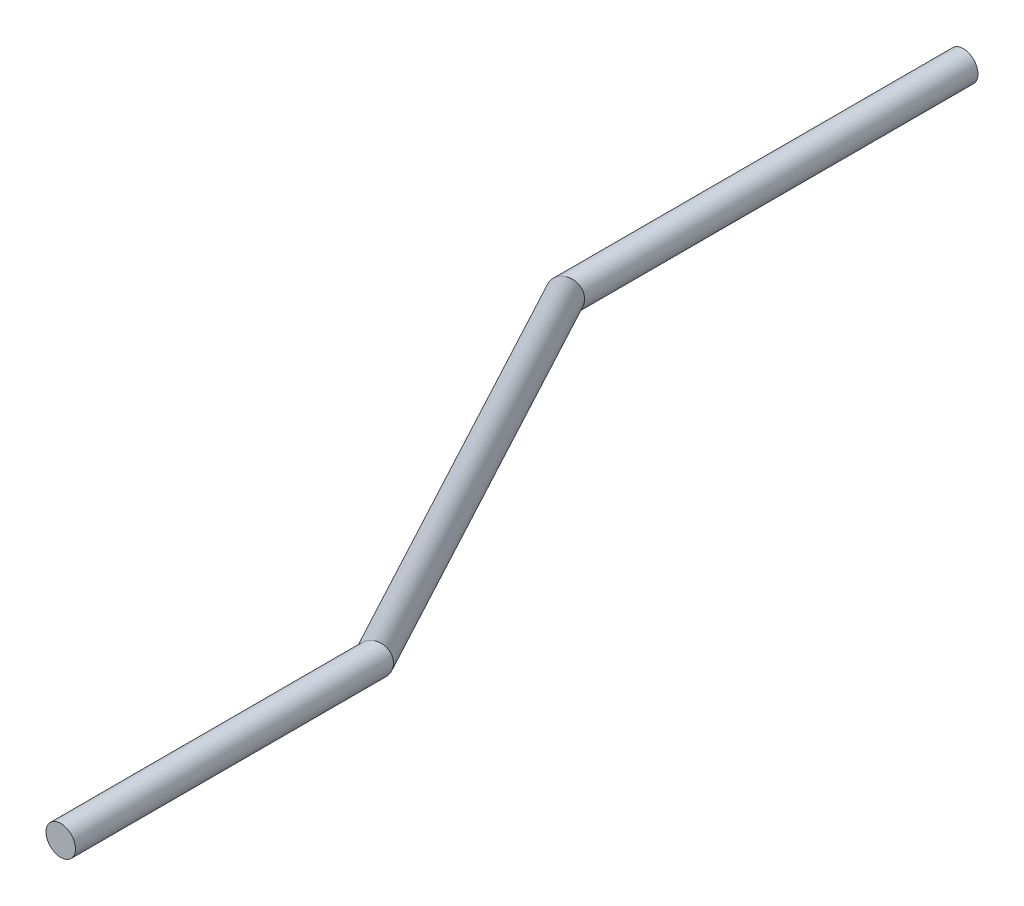
SolidWorks part; units mm, degrees
ref_plane "Front Plane" through (0, 0, 0) normal (0, 0, 1) x (1, 0, 0)
ref_plane "Top Plane" through (0, 0, 0) normal (0, 1, 0) x (1, 0, 0)
ref_plane "Right Plane" through (0, 0, 0) normal (1, 0, 0) x (0, 0, -1)
sketch3d "Route through both anchors"
  line L0 (-30, 0, -16.2) -> (-30, 0, 0)
  line L1 (-30, 0, 0) -> (-11.8202, 9.2349, 25.9599)
  line L2 (-11.8202, 9.2349, 25.9599) -> (-11.8202, 9.2349, 38.7099)
sweep "Round TPU cord - 1.2 mm" add path "Route through both anchors" circular profile diameter 1.2 parameters "D3"=1.2
